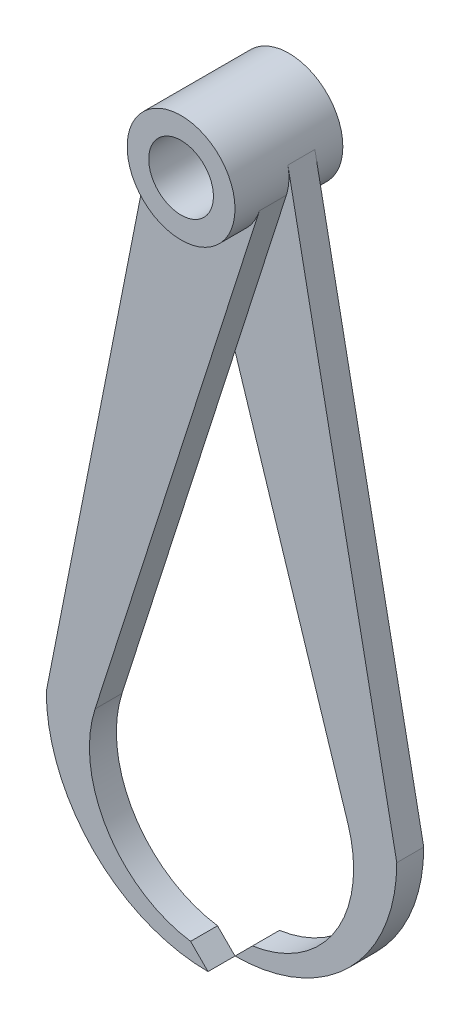
SolidWorks part; units mm, degrees
ref_plane "Front Plane" through (0, 0, 0) normal (0, 0, 1) x (1, 0, 0)
ref_plane "Top Plane" through (0, 0, 0) normal (0, 1, 0) x (1, 0, 0)
ref_plane "Right Plane" through (0, 0, 0) normal (1, 0, 0) x (0, 0, -1)
sketch "Sketch1" plane through (0, 0, 0) normal (0, 0, 1) x (1, 0, 0)
  line L0 (0, 0) -> (14259.5964, 0) construction
  line L1 (0, 0) -> (0, 14259.5964) construction
  line L4 (0, -130) -> (3.2399, -126.7601)
  line L5 (0, -130) -> (-3.2399, -126.7601)
  line L6 (30, -100) -> (9.8095, 1.9428)
  line L7 (20.9534, -98.2952) -> (-9.5243, -3.0476)
  line L8 (-30, -100) -> (-9.8095, 1.9428)
  line L9 (-20.9534, -98.2952) -> (9.5243, -3.0476)
  circle A4 centre (0, 0) radius 6
  circle A5 centre (0, 0) radius 10
  arc A6 (3.2399, -126.7601) -> (20.9534, -98.2952) centre (0, -105) ccw
  arc A7 (-30, -100) -> (30, -100) centre (0, -100) ccw
  arc A8 (-20.9534, -98.2952) -> (-3.2399, -126.7601) centre (0, -105) ccw
  dimension "D1" = 12
  dimension "D2" = 20
  dimension "D3" = 5
  dimension "D4" = 44
  dimension "D5" = 60
  dimension "D6" = 100
  dimension "D7" = 90
extrude "Boss-Extrude1" add sketch "Sketch1" along normal mid plane 20 contours A5 A4 region at (0, 9.7172, 0)
extrude "Boss-Extrude14" add sketch "Sketch1<52>" along normal blind 5 separate body contours A8 L9 L7 A5 L8 A7 L5 | A5 L7 L9 region at (-15.2871, -62.8373, 0) region at (0, -16.634, 0)
sketch "Sketch1<52>" plane through (0, 0, 0) normal (0, 0, 1) x (1, 0, 0) same geometry as "Sketch1"
extrude "Boss-Extrude15" add sketch "Sketch1<53>" against normal blind 5 separate body contours L4 A7 L6 A5 L9 L7 A6 | A5 L7 L9 region at (15.2871, -62.8373, 0) region at (0, -16.634, 0)
sketch "Sketch1<53>" plane through (0, 0, 0) normal (0, 0, 1) x (1, 0, 0) same geometry as "Sketch1"
